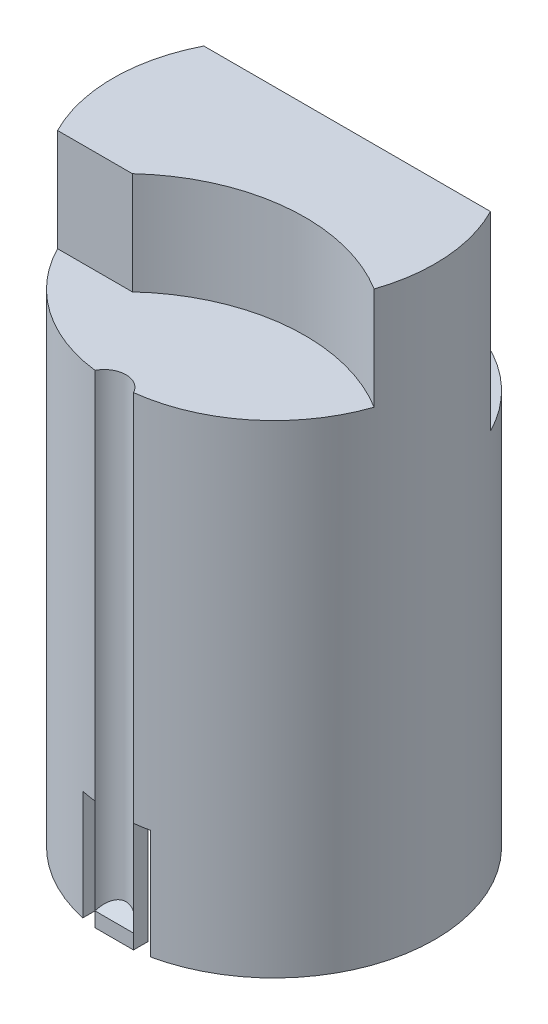
SolidWorks part; units mm, degrees
ref_plane "Front" through (0, 0, 0) normal (0, 0, 1) x (1, 0, 0)
ref_plane "Top" through (0, 0, 0) normal (0, 1, 0) x (1, 0, 0)
ref_plane "Right" through (0, 0, 0) normal (1, 0, 0) x (0, 0, -1)
sketch "Sketch1" plane through (0, 0, 0) normal (0, 1, 0) x (1, 0, 0)
  circle A0 centre (0, 0) radius 11
extrude "Boss-Extrude1" add sketch "Sketch1" along normal blind 40 contours A0
sketch "Sketch2" plane through (0, 40, 0) normal (0, 1, 0) x (1, 0, 0)
  line L0 (-9.798, 5) -> (9.798, 5)
  circle A1 centre (0, 0) radius 11 construction
  arc A2 (9.798, 5) -> (-9.798, 5) centre (0, 0) ccw
  dimension "D1" = 5
extrude "Cut-Extrude1" cut sketch "Sketch2" against normal blind 13
sketch "Sketch3" plane through (0, 40, 0) normal (0, 1, 0) x (1, 0, 0)
  line L0 (-9.798, -5) -> (-4.683, -5)
  arc A0 (-9.798, 5) -> (9.798, 5) centre (0, 0) ccw construction
  arc A3 (10.4065, -3.5645) -> (-4.683, -5) centre (3.8031, -14.178) ccw
  arc A8 (-9.798, -5) -> (10.4065, -3.5645) centre (0, 0) ccw
extrude "Cut-Extrude2" cut sketch "Sketch3" against normal blind 7
sketch "Sketch4" plane through (0, 33, 0) normal (0, 1, 0) x (1, 0, 0)
  arc A1 (1.3155, -10.9211) -> (-1.3155, -10.9211) centre (0, -11.6022) ccw
  arc A2 (-1.3155, -10.9211) -> (1.3155, -10.9211) centre (0, 0) ccw
extrude "Cut-Extrude3" cut sketch "Sketch4" against normal through all
sketch "Sketch6" plane through (0, 0, 0) normal (0, -1, 0) x (1, 0, 0)
  circle A0 centre (0, 0) radius 10
extrude "Cut-Extrude4" cut sketch "Sketch6" against normal offset from surface (25 mm away) 2 up to face at (0, 27, -8)
ref_plane "Plane1" through (0, 0, 12) normal (0, 0, 1) x (1, 0, 0)
sketch "Sketch7" plane through (0, 0, 12) normal (0, 0, 1) x (1, 0, 0)
  line L0 (-1.3155, 0) -> (-2.3155, 0)
  line L1 (-11, 0) -> (11, 0) construction
  line L2 (-2.3155, 0) -> (-2.3155, 7.5)
  line L3 (-2.3155, 7.5) -> (-1.3155, 7.5)
  line L4 (-1.3155, 0) -> (-1.3155, 33) construction
  line L5 (-1.3155, 7.5) -> (-1.3155, 0)
  line L6 (1.3155, 0) -> (1.3155, 7.5)
  line L7 (1.3155, 0) -> (1.3155, 33) construction
  line L8 (1.3155, 7.5) -> (2.3155, 7.5)
  line L9 (2.3155, 7.5) -> (2.3155, 0)
  line L10 (2.3155, 0) -> (1.3155, 0)
extrude "Cut-Extrude5" cut sketch "Sketch7" against normal blind 7
sketch "Sketch8" plane through (0, 0, 0) normal (0, -1, 0) x (1, 0, 0)
  line L0 (-1.3155, 10.9211) -> (1.3155, 10.9211)
  line L1 (1.3155, 10.9211) -> (1.3155, 9.9131)
  line L2 (1.3155, 9.9131) -> (-1.3155, 9.9131)
  line L3 (-1.3155, 9.9131) -> (-1.3155, 10.9211)
extrude "Boss-Extrude2" add sketch "Sketch8" against normal blind 2
chamfer "Chamfer1" distance 1 angle 45 1 edges at (0, 2, 10.9211)
